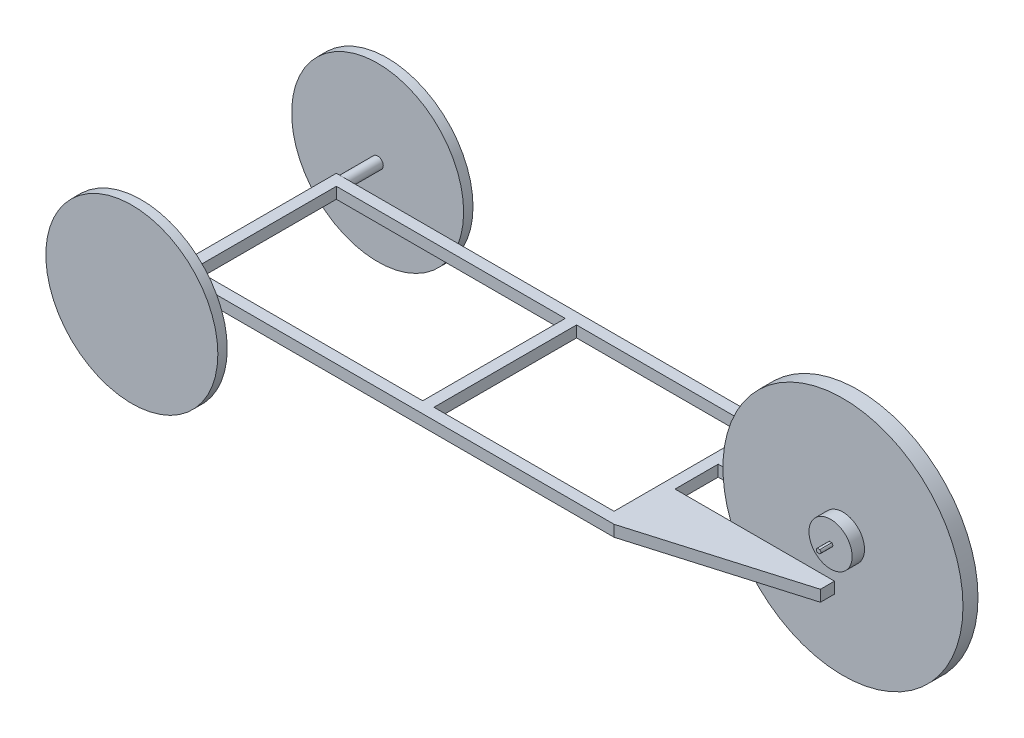
SolidWorks part; units mm, degrees
ref_plane "Front Plane" through (0, 0, 0) normal (0, 0, 1) x (1, 0, 0)
ref_plane "Top Plane" through (0, 0, 0) normal (0, 1, 0) x (1, 0, 0)
ref_plane "Right Plane" through (0, 0, 0) normal (1, 0, 0) x (0, 0, -1)
sketch "Sketch2" plane through (0, 0, 0) normal (0, 1, 0) x (1, 0, 0)
  line L0 (-560, 190) -> (-560, -190)
  line L4 (-560, 190) -> (560, 190)
  line L5 (560, 190) -> (560, -190)
  line L6 (560, -190) -> (-560, -190)
  line L8 (80, 190) -> (80, -190)
  line L9 (50, -190) -> (50, 190)
  line L10 (-560, -190) -> (560, 190) construction
  line L11 (-590, 220) -> (590, 220)
  line L12 (-590, 220) -> (-590, -220)
  line L13 (-590, -220) -> (590, -220)
  line L14 (590, 220) -> (590, -220)
  line L15 (-590, 220) -> (590, -220) construction
  line L16 (-590, 0) -> (-560, 0) construction
  line L17 (50, 0) -> (80, 0) construction
  point P3 (-413.2718, -88.1724)
  point P23 (-423.9586, 89.0961)
  dimension "D1" = 30
  dimension "D2" = 30
  dimension "D3" = 440
  dimension "D4" = 1180
  dimension "D5" = 540
extrude "Boss-Extrude1" add sketch "Sketch2" along normal blind 15 and the other way blind 15 contours L14 L11 L12 L13 L5 L6 L0 L4 | L9 L6 L8 L4 region at (65, 0, 0) region at (0, 0, -207.4064)
sketch "Sketch3" plane through (0, 0, 0) normal (0, 0, 1) x (1, 0, 0)
  line L0 (-590, -15) -> (590, -15) construction
  line L1 (-590, -15) -> (-590, 15) construction
  line L2 (-590, 15) -> (590, 15) construction
  circle A0 centre (-575, 0) radius 15
extrude "Boss-Extrude2" add sketch "Sketch3" along normal blind 315 and the other way blind 315
sketch "Sketch4" plane through (0, 0, 315) normal (0, 0, 1) x (1, 0, 0)
  circle A0 centre (-575, 0) radius 229.2
  dimension "D1" = 458.4
extrude "Boss-Extrude3" add sketch "Sketch4" along normal blind 25
mirror "Mirror1" about plane through (0, 0, 0) normal (0, 0, 1) of "Boss-Extrude3"
sketch "Sketch5" plane through (0, 0, 0) normal (0, 0, 1) x (1, 0, 0)
  line L0 (1000, 90.7) -> (-590, 0) construction
  line L1 (-590, -15) -> (-590, 0) construction
  line L2 (-575, -229.2) -> (1000, -229.2) construction
  line L3 (-575, 0) -> (-575, -229.2) construction
  circle A0 centre (1000, 90.7) radius 319.9
  circle A1 centre (-575, 0) radius 15 construction
  circle A2 centre (-575, 0) radius 229.2 construction
  dimension "D2" = 639.8
  dimension "D1" = 1590
extrude "Boss-Extrude4" add sketch "Sketch5" along normal blind 20 and the other way blind 20 separate body
sketch "Sketch6" plane through (0, 0, 0) normal (0, 0, 1) x (1, 0, 0)
  circle A0 centre (1000, 90.7) radius 57.5
  dimension "D1" = 115
extrude "Boss-Extrude5" add sketch "Sketch6" along normal blind 53 and the other way blind 43
sketch "Sketch7" plane through (0, 0, 0) normal (0, 0, 1) x (1, 0, 0)
  line L0 (996.6834, 95.7) -> (1003.3166, 95.7)
  line L1 (996.6834, 85.7) -> (1003.3166, 85.7)
  line L2 (1000, 85.7) -> (1000, 95.7) construction
  circle A0 centre (1000, 90.7) radius 6
  point P9 (0, 0)
  dimension "D2" = 12
  dimension "D1" = 10
extrude "Boss-Extrude6" add sketch "Sketch7" along normal blind 85 and the other way blind 75 contours L2 L1 A0 L0 | L1 L2 L0 A0 region at (997.3422, 90.7, 0) region at (1002.6578, 90.7, 0)
sketch "Sketch8" plane through (0, 0, 0) normal (0, 1, 0) x (1, 0, 0)
  line L0 (590, -220) -> (1015, -95)
  line L1 (1015, -95) -> (1015, 95)
  line L2 (1015, 95) -> (590, 220)
  line L3 (590, 220) -> (590, 57.5)
  line L4 (590, 220) -> (590, -220) construction
  line L5 (590, 57.5) -> (985, 57.5)
  line L6 (985, 57.5) -> (985, -57.5)
  line L7 (985, -57.5) -> (590, -57.5)
  line L8 (590, -57.5) -> (590, -220)
  line L9 (985, -57.5) -> (1015, -57.5)
  line L10 (985, 57.5) -> (1015, 57.5)
  line L11 (985, 0) -> (590, 0) construction
  line L12 (1000, 75) -> (1000, 0) construction
  line L13 (996.6834, 75) -> (1003.3166, 75) construction
  line L14 (985, 0) -> (1015, 0) construction
  dimension "D1" = 30
  dimension "D2" = 115
  dimension "D3" = 95
extrude "Boss-Extrude7" add sketch "Sketch8" against normal up to surface (15 mm away) and the other way up to surface (15 mm away) contours L9 L7 L8 L0 L1 | L5 L10 L1 L2 L3 region at (758.2292, 0, 114.0104) region at (758.2292, 0, -114.0104) up to face at (-191.6667, -15, 0) other way up to face at (-191.6667, 15, 0)
